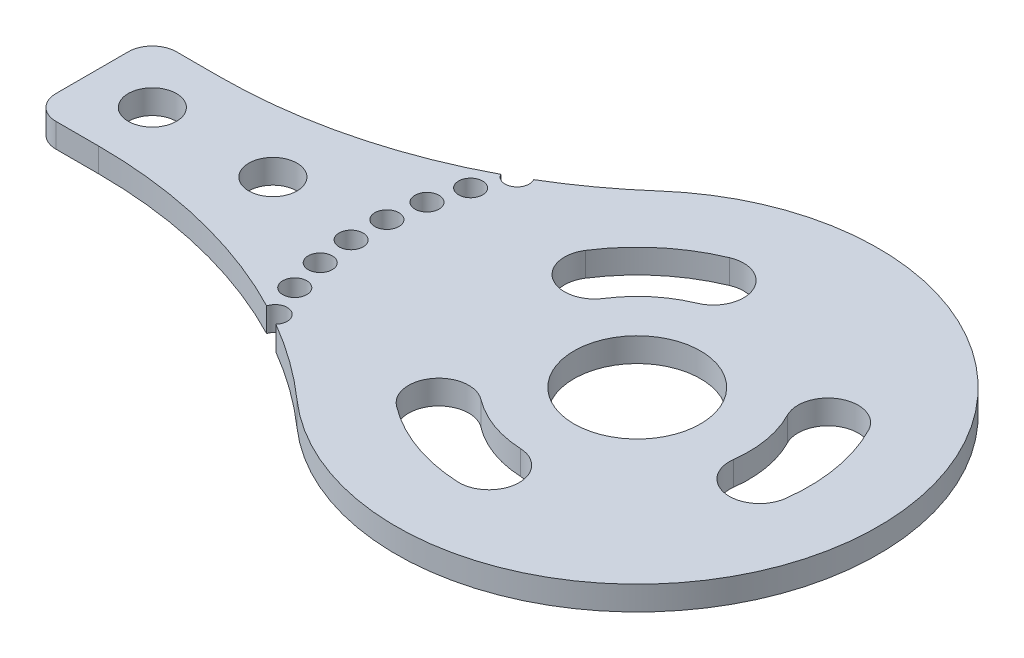
SolidWorks part; units mm, degrees
material "Стеклотекстолит"
ref_plane "Спереди" through (0, 0, 0) normal (0, 0, 1) x (1, 0, 0)
ref_plane "Сверху" through (0, 0, 0) normal (0, 1, 0) x (1, 0, 0)
ref_plane "Справа" through (0, 0, 0) normal (1, 0, 0) x (0, 0, -1)
sketch "Эскиз1" plane through (0, 0, 0) normal (0, 1, 0) x (1, 0, 0)
  line L0 (0, -2) -> (0, -8)
  line L1 (2, -10) -> (5.5425, -10)
  line L2 (2, 0) -> (5.5425, 0)
  line L3 (5.5425, 0) -> (5.5425, -10) construction
  arc A0 (32, -20) -> (32, 10) centre (45.2288, -5) ccw
  arc A1 (5.5425, -10) -> (32, -20) centre (5.5425, -50) cw
  arc A2 (5.5425, 0) -> (32, 10) centre (5.5425, 40) ccw
  arc A3 (0, -8) -> (2, -10) centre (2, -8) ccw
  arc A4 (0, -2) -> (2, 0) centre (2, -2) cw
  point P12 (0, -10)
  point P15 (0, 0)
  dimension "D2" = 40
  dimension "D3" = 2
  dimension "D4" = 20
  dimension "D1" = 10
  dimension "D5" = 32
extrude "Бобышка-Вытянуть1" add sketch "Эскиз1" along normal blind 2
sketch "Эскиз2" plane through (0, 2, 0) normal (0, 1, 0) x (1, 0, 0)
  circle A2 centre (25.1372, 5.1281) radius 1
  circle A4 centre (45.2288, -5) radius 22.5 construction
  arc A5 (32, -20) -> (32, 10) centre (45.2288, -5) ccw construction
  arc A6 (5.5425, 0) -> (32, 10) centre (5.5425, 40) ccw construction
  dimension "D1" = 2
  dimension "D2" = 45
extrude "Вырез-Вытянуть1" cut sketch "Эскиз2" against normal through all
pattern_circular "Круговой массив1" count 8 every 7.5 about axis through (45.2288, 2, 5) along (0, 1, 0) of "Вырез-Вытянуть1"
sketch "Эскиз3" plane through (0, 2, 0) normal (0, 1, 0) x (1, 0, 0)
  line L0 (0, -2) -> (0, -8) construction
  line L3 (5, -10) -> (5, 0) construction
  line L4 (2, -10) -> (5.5425, -10) construction
  line L5 (5.5425, 0) -> (2, 0) construction
  circle A0 centre (5, -5) radius 2
  dimension "D1" = 4
  dimension "D2" = 5
extrude "Вырез-Вытянуть2" cut sketch "Эскиз3" against normal through all
pattern_linear "Линейный массив1" count 2 spacing 10 along (1, 0, 0) of "Вырез-Вытянуть2"
sketch "Эскиз4" plane through (0, 2, 0) normal (0, 1, 0) x (1, 0, 0)
  circle A0 centre (45.2288, -5) radius 11.75 construction
  arc A1 (32, -20) -> (32, 10) centre (45.2288, -5) ccw construction
  circle A2 centre (45.2288, 6.75) radius 2
  dimension "D1" = 4
  dimension "D2" = 23.5
extrude "Вырез-Вытянуть3" [suppressed] cut sketch "Эскиз4" against normal through all
pattern_circular "Круговой массив2" [suppressed] count 8 every 45 of bodies 108
sketch "Эскиз6" plane through (0, 2, 0) normal (0, 1, 0) x (1, 0, 0)
  line L0 (45.2288, -5) -> (34.7269, 5.5019) construction
  line L1 (45.2288, -5) -> (35.4788, -5) construction
  arc A0 (41.6704, 3.5381) -> (37.4462, -0.0008) centre (45.2288, -5) ccw
  arc A1 (32, -20) -> (32, 10) centre (45.2288, -5) ccw construction
  arc A2 (39.747, 8.1533) -> (33.2394, 2.7016) centre (45.2288, -5) ccw
  circle A4 centre (35.3428, 1.3504) radius 2.5
  circle A5 centre (40.7087, 5.8457) radius 2.5
  circle M8 centre (15, -5) radius 2
  dimension "D1" = 5
  dimension "D2" = 5
  dimension "D3" = 45
  dimension "D4" = 11.7499
  dimension "D5" = 7
extrude "Вырез-Вытянуть4" cut sketch "Эскиз6" against normal through all contours A4 | A5 A2 A4 A0 | A5 M8 region at (37.5163, 2, -4.2062) region at (40.7087, 2, -5.8457) region at (35.3428, 2, -1.3504)
pattern_circular "Круговой массив3" count 3 every 120 about axis through (45.2288, 2, 5) along (0, 1, 0) of "Вырез-Вытянуть4"
sketch "Эскиз7" plane through (0, 2, 0) normal (0, 1, 0) x (1, 0, 0)
  circle A0 centre (45.2288, -5) radius 5.25
  arc A1 (32, -20) -> (32, 10) centre (45.2288, -5) ccw construction
  dimension "D1" = 10.5
extrude "Вырез-Вытянуть5" cut sketch "Эскиз7" against normal through all
equation "\"thick\"= \"thick@балка.SLDASM\""
equation "\"D1@Бобышка-Вытянуть1\"=\"thick\""
